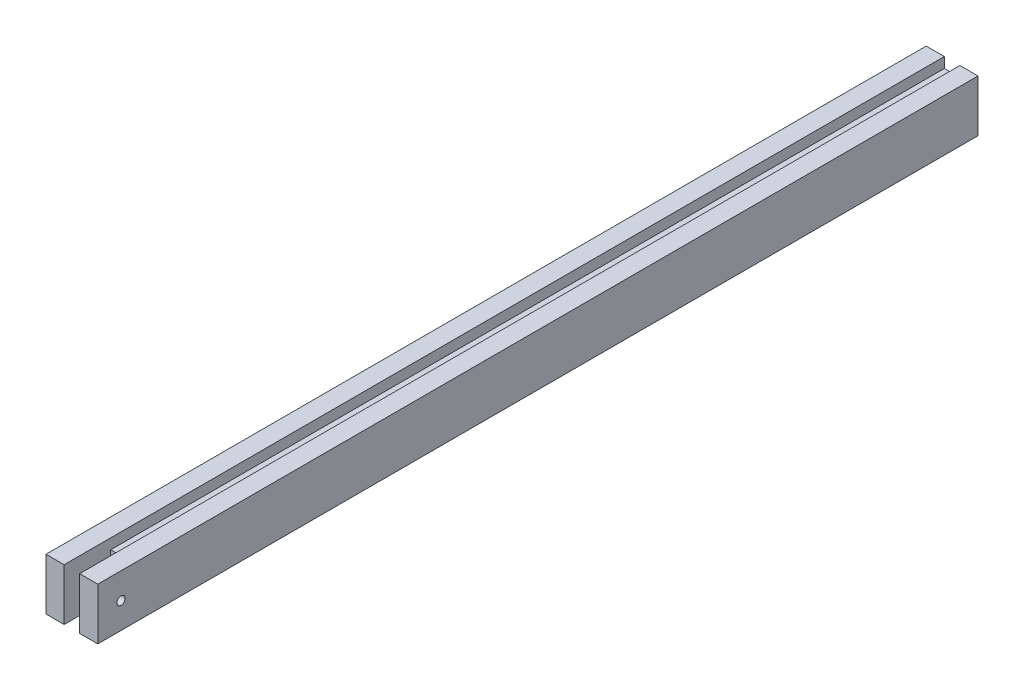
SolidWorks part; units mm, degrees
ref_plane "Front" through (0, 0, 0) normal (0, 0, 1) x (1, 0, 0)
ref_plane "Top" through (0, 0, 0) normal (0, 1, 0) x (1, 0, 0)
ref_plane "Right" through (0, 0, 0) normal (1, 0, 0) x (0, 0, -1)
sketch "Esquisse1" plane through (0, 0, 0) normal (0, 0, 1) x (1, 0, 0)
  line L1 (0, 0) -> (100, 0)
  line L2 (0, 0) -> (0, 100)
  line L3 (0, 100) -> (100, 100)
  line L4 (100, 0) -> (100, 100)
  dimension "D1" = 100
  dimension "D2" = 100
extrude "Boss.-Extru.1" add sketch "Esquisse1" along normal blind 1700
sketch "Esquisse2" plane through (0, 0, 0) normal (0, -1, 0) x (1, 0, 0)
  line L0 (0, 1700) -> (100, 1700) construction
  line L1 (35, 1700) -> (65, 1700)
  line L2 (35, 1700) -> (35, 1610)
  line L3 (35, 1610) -> (65, 1610)
  line L4 (65, 1700) -> (65, 1610)
  line L5 (50, 1610) -> (50, 1700) construction
  dimension "D1" = 30
  dimension "D2" = 90
extrude "Enlèv. mat.-Extru.1" cut sketch "Esquisse2" against normal through all
sketch "Esquisse3" plane through (100, 0, 0) normal (1, 0, 0) x (0, 0, -1)
  line L0 (-1700, 50) -> (-1655, 50) construction
  line L1 (-1700, 0) -> (-1700, 100) construction
  line L2 (-1655, 50) -> (-1610, 50) construction
  line L3 (-1610, 100) -> (-1610, 0) construction
  circle A0 centre (-1655, 50) radius 8
  dimension "D1" = 16
extrude "Enlèv. mat.-Extru.2" cut sketch "Esquisse3" against normal through all
sketch "Esquisse4" plane through (0, 0, 0) normal (0, 0, -1) x (-1, 0, 0)
  line L0 (0, 50) -> (-100, 50) construction
  line L4 (0, 100) -> (0, 0) construction
  line L5 (-100, 0) -> (-100, 100) construction
  line L6 (-100, 100) -> (0, 100) construction
  line L7 (-65, 100) -> (-35, 100)
  line L8 (-65, 100) -> (-65, 80)
  line L9 (-65, 80) -> (-35, 80)
  line L10 (-35, 100) -> (-35, 80)
  line L11 (-50, 80) -> (-50, 50) construction
  line L12 (-35, 0) -> (-35, 20)
  line L13 (-65, 20) -> (-35, 20)
  line L14 (-65, 0) -> (-65, 20)
  line L15 (-65, 0) -> (-35, 0)
  dimension "D1" = 20
  dimension "D2" = 30
extrude "Enlèv. mat.-Extru.3" cut sketch "Esquisse4" against normal through all
